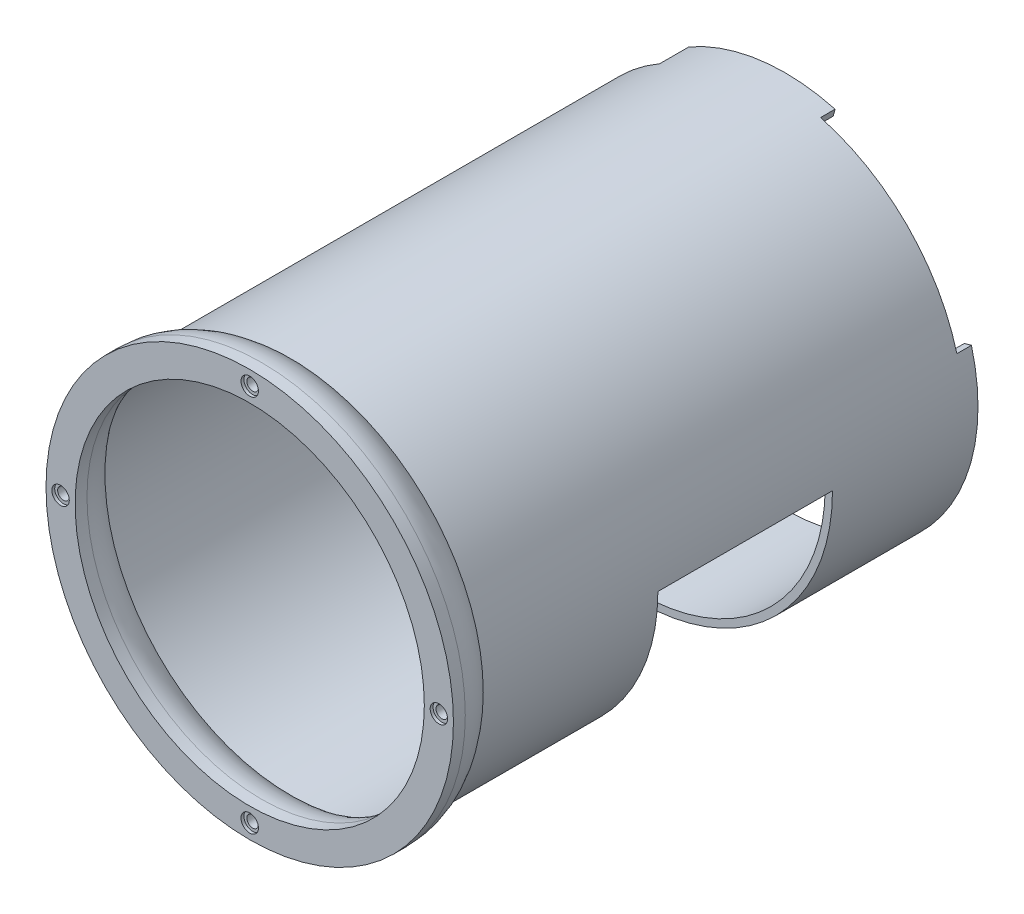
SolidWorks part; units mm, degrees
ref_plane "Ebene vorne" through (0, 0, 0) normal (1, 0, 0) x (0, 1, 0)
ref_plane "Ebene oben" through (0, 0, 0) normal (0, 0, 1) x (0, 1, 0)
ref_plane "Ebene rechts" through (0, 0, 0) normal (0, 1, 0) x (-1, 0, 0)
sketch "Skizze1" plane through (0, 0, 0) normal (0, 0, 1) x (0, 1, 0)
  circle A0 centre (0, 0) radius 60
  circle A1 centre (0, 0) radius 70
  dimension "D1" = 120
  dimension "D2" = 140
extrude "Aufsatz-Linear austragen1" add sketch "Skizze1" against normal blind 14
sketch "Skizze3" plane through (0, 0, 0) normal (0, 0, 1) x (0, 1, 0)
  line L0 (-70, 0) -> (70, 0) construction
  line L1 (0, -70) -> (0, 70) construction
  circle A0 centre (0, 0) radius 70 construction
  circle A1 centre (0, 0) radius 65 construction
  circle A2 centre (-65, 0) radius 2
  circle A3 centre (0, 65) radius 2
  circle A4 centre (65, 0) radius 2
  circle A5 centre (0, -65) radius 2
  dimension "D1" = 130
sketch "Skizze10" plane through (0, 0, 0) normal (0, 0, 1) x (1, 0, 0)
  circle A0 centre (0, 0) radius 63.75
  circle A1 centre (0, 0) radius 66.25
extrude "Aufsatz-Linear austragen2" add sketch "Skizze10" against normal blind 170 from offset 14 offset against normal yes
sketch "Skizze4" plane through (0, 0, 0) normal (0, 0, 1) x (0, 1, 0)
  line L1 (0, -70) -> (0, 70) construction
  line L2 (-70, 0) -> (70, 0) construction
  line L3 (-70, 0) -> (-60, 0)
  line L4 (0, -60) -> (0, -70)
  arc A0 (-70, 0) -> (0, -70) centre (0, 0) ccw
  arc A2 (-60, 0) -> (0, -60) centre (0, 0) ccw
  circle A4 centre (0, 0) radius 60 construction
extrude "Schnitt-Linear austragen1" cut sketch "Skizze4" along normal blind 60 from offset 134 offset against normal yes
sketch "Skizze5" plane through (0, 0, 0) normal (0, 0, 1) x (0, 1, 0)
  line L1 (30, 51.9615) -> (35, 60.6218)
  line L26 (60.6218, 35) -> (51.9615, 30)
  arc A4 (35, 60.6218) -> (60.6218, 35) centre (0, 0) cw
  arc A5 (30, 51.9615) -> (51.9615, 30) centre (0, 0) cw
extrude "Schnitt-Linear austragen3" cut sketch "Skizze5" along normal blind 10 from offset 184 offset against normal yes
sketch "Skizze6" plane through (0, 0, 0) normal (0, 0, 1) x (0, 1, 0)
  line L88 (57.9555, -15.5291) -> (67.6148, -18.1173)
  line L101 (15.5291, -57.9555) -> (18.1173, -67.6148)
  arc A3 (67.6148, -18.1173) -> (18.1173, -67.6148) centre (0, 0) cw
  arc A4 (57.9555, -15.5291) -> (15.5291, -57.9555) centre (0, 0) cw
extrude "Schnitt-Linear austragen4" cut sketch "Skizze6" along normal blind 5 from offset 184 contours L101 A3 L88 A4 offset against normal yes
extrude "Schnitt-Linear austragen5" cut sketch "Skizze3" against normal blind 7
sketch "Skizze9" plane through (0, 0, 0) normal (0, 0, 1) x (0, 1, 0)
  circle A0 centre (0, 65) radius 3
  circle A1 centre (65, 0) radius 3
  circle A2 centre (0, -65) radius 3
  circle A3 centre (-65, 0) radius 3
extrude "Schnitt-Linear austragen6" cut sketch "Skizze9" against normal blind 1
fillet "Verrundung4" radius 15 1 edges at (60, 0, -14)
fillet "Verrundung5" radius 15 1 edges at (70, 0, -14)
